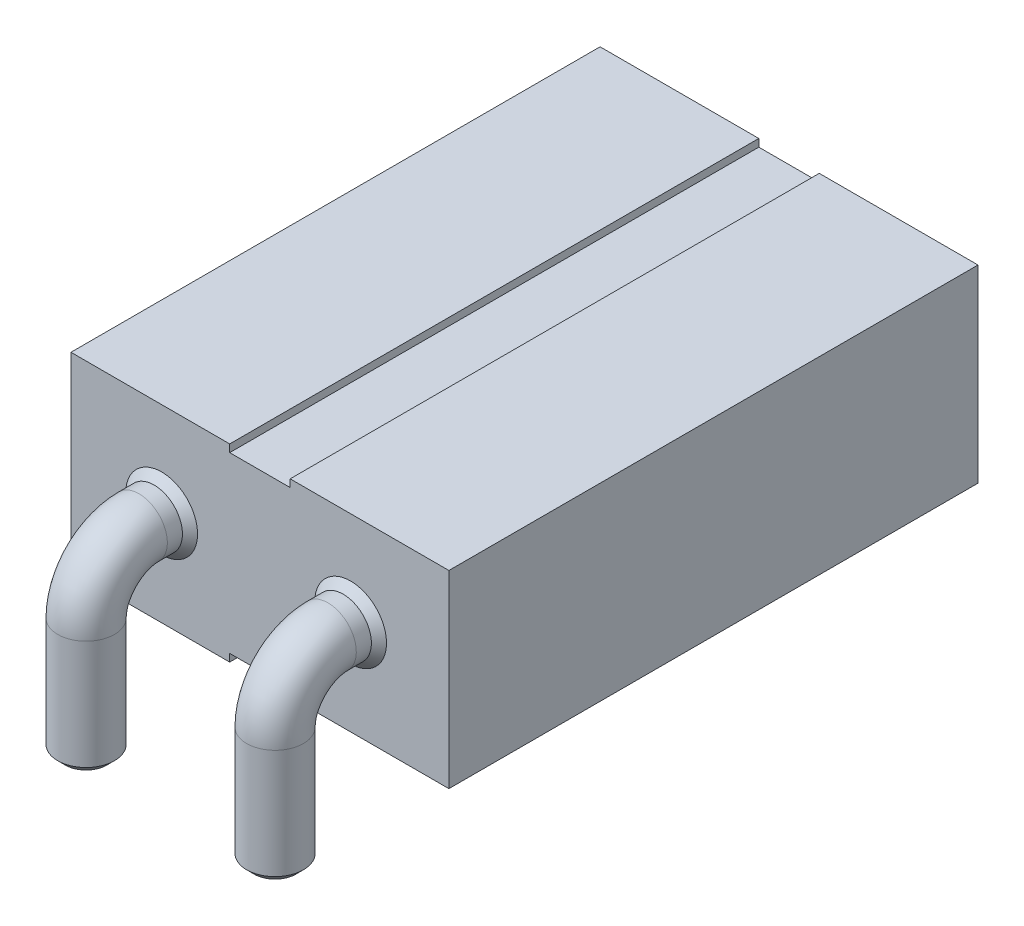
SolidWorks part; units mm, degrees
ref_plane "Front" through (0, 0, 0) normal (0, 0, 1) x (1, 0, 0)
ref_plane "Top" through (0, 0, 0) normal (0, 1, 0) x (1, 0, 0)
ref_plane "Right" through (0, 0, 0) normal (1, 0, 0) x (0, 0, -1)
sketch "Sketch1" plane through (0, 0, 0) normal (0, 1, 0) x (1, 0, 0)
  line L1 (-2.5, -3.5) -> (2.5, -3.5)
  line L2 (-2.5, -3.5) -> (-2.5, 3.5)
  line L3 (-2.5, 3.5) -> (2.5, 3.5)
  line L4 (2.5, -3.5) -> (2.5, 3.5)
  line L5 (-2.5, -3.5) -> (2.5, 3.5) construction
  line L6 (-2.5, 3.5) -> (2.5, -3.5) construction
  point P0 (0, 0)
  dimension "D1" = 5
  dimension "D2" = 7
extrude "Boss-Extrude1" add sketch "Sketch1" along normal blind 2.5
ref_plane "Plane1" through (0, 1.25, 0) normal (0, -1, 0) x (-1, 0, 0)
ref_axis "Axis1" through (2.5, 1.25, -3.5) along (-1, 0, 0)
sketch "Sketch2" plane through (0, 0, -3.5) normal (0, 0, -1) x (-1, 0, 0)
  line L0 (-2.5, 1.25) -> (2.5, 1.25) construction
  line L1 (-2.5, 2.5) -> (-2.5, 0) construction
  circle A0 centre (-1.2, 1.25) radius 0.75
  dimension "D1" = 1.5
  dimension "D2" = 1.3
extrude "Cut-Extrude1" cut sketch "Sketch2" against normal blind 6.5
ref_plane "Plane2" through (1.2, 0, 0) normal (1, 0, 0) x (0, 0, -1)
sketch "Sketch3" plane through (1.2, 0, 0) normal (1, 0, 0) x (0, 0, -1)
  line L0 (-3.5, 1.2542) -> (-3.8, 1.2542)
  line L1 (-4.5, 0.5542) -> (-4.5, -0.993)
  line L2 (-3.5, 2.5) -> (-3.5, 0) construction
  arc A0 (-3.8, 1.2542) -> (-4.5, 0.5542) centre (-3.8, 0.5542) ccw
  point P7 (-4.5, 1.2542)
  dimension "D2" = 0.7
  dimension "D1" = 1
sketch "Sketch4" plane through (0, 0, 3.5) normal (0, 0, 1) x (1, 0, 0)
  circle A0 centre (1.2, 1.2542) radius 0.375
  dimension "D1" = 0.75
sweep "Sweep1" add profiles "Sketch4" path "Sketch3"
chamfer "Chamfer1" distance 0.1 angle 45 2 edges at (0.825, 1.2542, 3.5) (1.575, -0.993, 4.5)
sketch "Sketch5" plane through (0, 0, -3.5) normal (0, 0, -1) x (-1, 0, 0)
  line L1 (-2.5, 2.5) -> (2.5, 2.5) construction
  line L2 (-0.4, 2.4) -> (0.4, 2.4)
  line L3 (-0.4, 2.4) -> (-0.4, 2.5)
  line L4 (-0.4, 2.5) -> (0.4, 2.5)
  line L5 (0.4, 2.4) -> (0.4, 2.5)
  line L6 (-0.4, 2.4) -> (0.4, 2.5) construction
  line L7 (-0.4, 2.5) -> (0.4, 2.4) construction
  line L9 (-2.5, 2.5) -> (-2.5, 0) construction
  point P0 (0, 2.45)
  dimension "D1" = 0.1
  dimension "D2" = 0.8
  dimension "D3" = 2.5
extrude "Cut-Extrude2" cut sketch "Sketch5" against normal through all
mirror "Mirror6" about plane through (0, 1.25, 0) normal (0, -1, 0) of "Cut-Extrude2"
pattern_linear "LPattern1" count 2 spacing 2.5 along (-1, 0, 0) of "Cut-Extrude1"
pattern_linear "LPattern2" count 2 spacing 2.5 along (-1, 0, 0) of "Sweep1", "Chamfer1"
